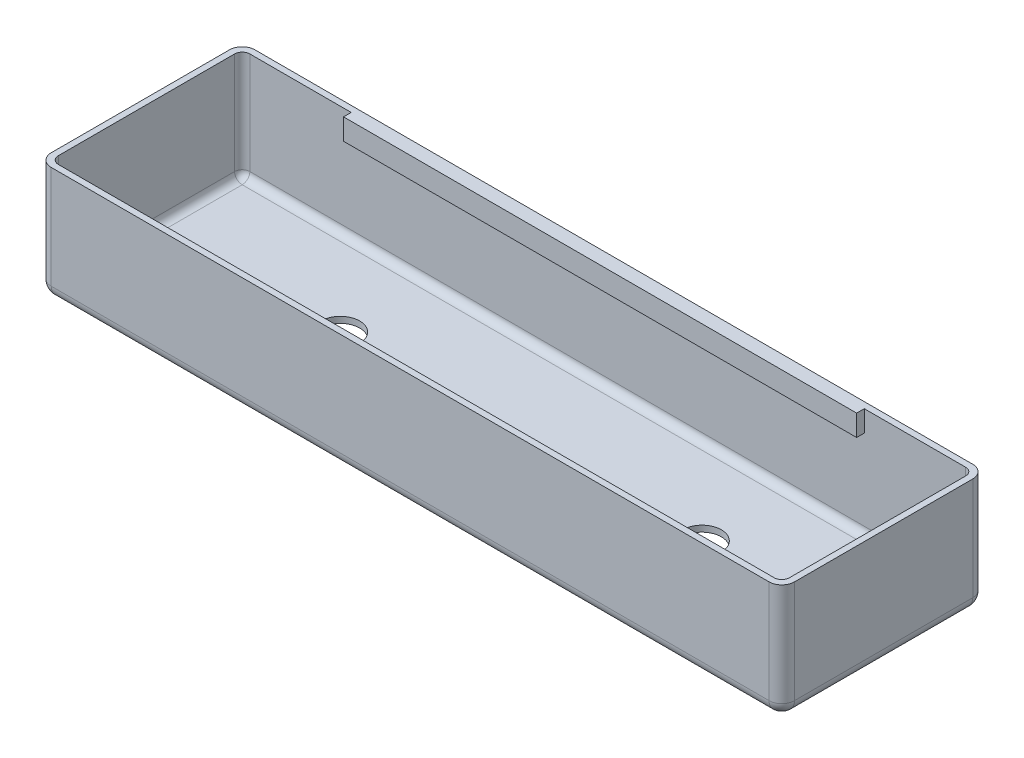
SolidWorks part; units mm, degrees
material "NEOPRENE"
ref_plane "Front" through (0, 0, 0) normal (0, 0, 1) x (1, 0, 0)
ref_plane "Top" through (0, 0, 0) normal (0, 1, 0) x (1, 0, 0)
ref_plane "Right" through (0, 0, 0) normal (1, 0, 0) x (0, 0, -1)
sketch "Sketch1" plane through (0, 0, 0) normal (0, 1, 0) x (1, 0, 0)
  line L0 (-91.1606, 0) -> (-92.6846, 0) construction
  line L1 (-92.6846, 25.4) -> (92.6846, 25.4)
  line L2 (-92.6846, 25.4) -> (-92.6846, -25.4)
  line L3 (-92.6846, -25.4) -> (92.6846, -25.4)
  line L4 (92.6846, 25.4) -> (92.6846, -25.4)
  line L5 (-92.6846, 25.4) -> (92.6846, -25.4) construction
  line L6 (-92.6846, -25.4) -> (92.6846, 25.4) construction
  line L7 (91.1606, 23.876) -> (-91.1606, 23.876)
  line L8 (91.1606, 23.876) -> (91.1606, -23.876)
  line L9 (91.1606, -23.876) -> (-91.1606, -23.876)
  line L10 (-91.1606, 23.876) -> (-91.1606, -23.876)
  line L11 (91.1606, 23.876) -> (-91.1606, -23.876) construction
  line L12 (91.1606, -23.876) -> (-91.1606, 23.876) construction
  line L13 (0, 23.876) -> (0, 25.4) construction
  point P0 (0, 0)
  point P6 (0, 0)
  dimension "D1" = 182.3212
  dimension "D2" = 50.8
  dimension "THICKNESS" = 1.524
extrude "Boss-Extrude1" add sketch "Sketch1" along normal blind 27.305
sketch "Sketch2" plane through (0, 0, 0) normal (0, -1, 0) x (1, 0, 0)
  line L4 (92.6846, -25.4) -> (92.6846, 25.4)
  line L5 (92.6846, 25.4) -> (-92.6846, 25.4)
  line L6 (-92.6846, 25.4) -> (-92.6846, -25.4)
  line L7 (-92.6846, -25.4) -> (92.6846, -25.4)
  line L8 (92.6846, -25.4) -> (92.6846, 25.4)
  line L9 (92.6846, 25.4) -> (-92.6846, 25.4)
  line L10 (-92.6846, 25.4) -> (-92.6846, -25.4)
  line L11 (-92.6846, -25.4) -> (92.6846, -25.4)
  dimension "D1" = 0
extrude "Boss-Extrude2" add sketch "Sketch2" along normal blind 1.524
fillet "Fillet1" radius 1.905 7 edges at (91.1606, 13.6525, 23.876) (-91.1606, 13.6525, 23.876) (-91.1606, 13.6525, -23.876) (91.1606, 0, 0) (0, 0, 23.876) (-91.1606, 0, 0) (0, 0, -23.876)
fillet "Fillet2" radius 3.175 8 edges at (-92.6846, -1.524, 0) (0, -1.524, 25.4) (92.6846, -1.524, 0) (0, -1.524, -25.4) (-92.6846, 12.8905, -25.4) (92.6846, 12.8905, -25.4) (92.6846, 12.8905, 25.4) (-92.6846, 12.8905, 25.4)
sketch "Sketch3" plane through (0, -1.524, 0) normal (0, -1, 0) x (1, 0, 0)
  circle A0 centre (45, -2.3792) radius 4.826
  circle A1 centre (-45.2, -2.3792) radius 4.826
  dimension "D1" = 9.652
extrude "Cut-Extrude1" cut sketch "Sketch3" against normal through all and the other way blind 2.54
sketch "Sketch4" [suppressed] plane through (0, -1.524, 0) normal (0, -1, 0) x (1, 0, 0)
  line L0 (-89.5096, 25.4) -> (89.5096, 25.4) construction
  line L1 (92.6846, 22.225) -> (92.6846, -22.225) construction
  circle A0 centre (67.2846, 6.35) radius 12.7
  dimension "D1" = 25.4
  dimension "D2" = 19.05
  dimension "D3" = 25.4
extrude "Cut-Extrude2" [suppressed] cut sketch "Sketch4" against normal through all
sketch "Sketch5" plane through (0, 0, -23.876) normal (0, 0, 1) x (1, 0, 0)
  line L0 (0, 0) -> (0, 24.6678) construction
  line L1 (89.2556, 27.305) -> (-89.2556, 27.305) construction
  line L2 (-63.9809, 22.0307) -> (63.9809, 22.0307)
  line L3 (-63.9809, 22.0307) -> (-63.9809, 27.305)
  line L4 (-63.9809, 27.305) -> (63.9809, 27.305)
  line L5 (63.9809, 22.0307) -> (63.9809, 27.305)
  line L6 (-63.9809, 22.0307) -> (63.9809, 27.305) construction
  line L7 (-63.9809, 27.305) -> (63.9809, 22.0307) construction
  dimension "D1" = 127.9618
  dimension "D2" = 5.2743
extrude "Boss-Extrude3" add sketch "Sketch5" along normal blind 1.905
fillet "Fillet3" [suppressed] radius 0.9525
equation "\"D1@Boss-Extrude2\"=\"THICKNESS\""
